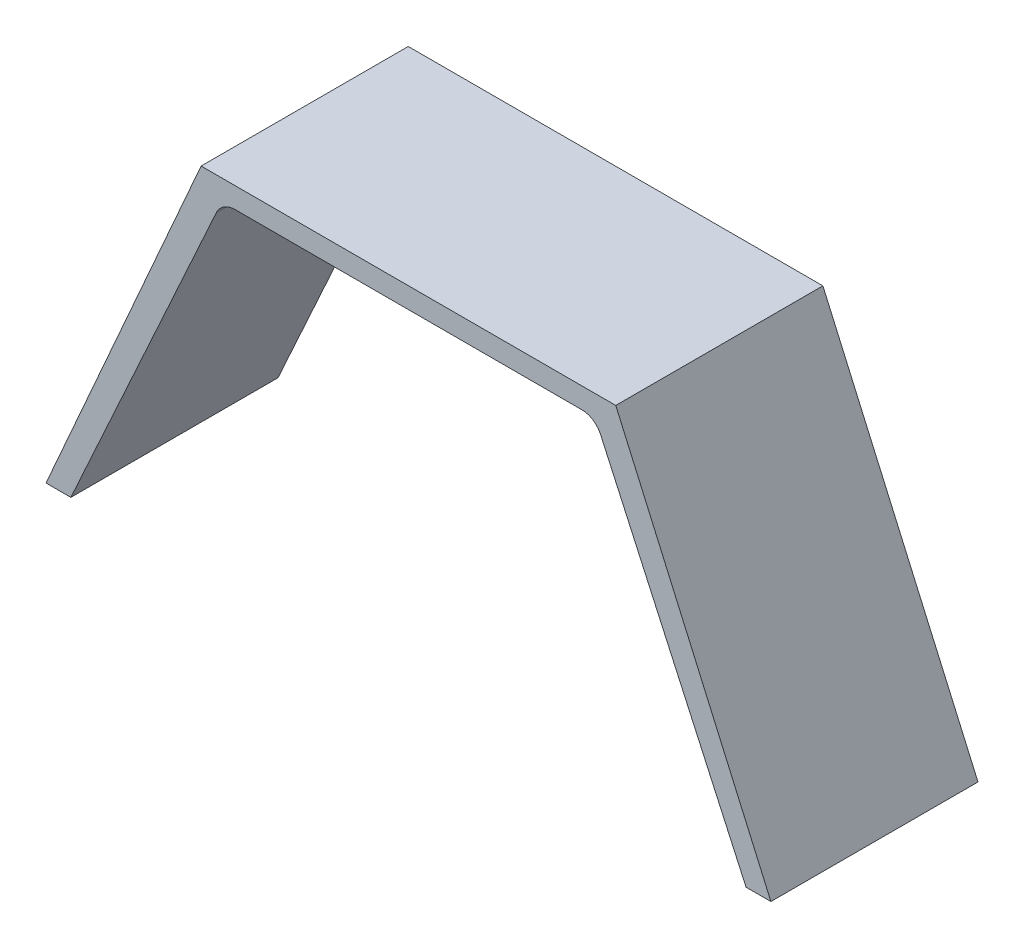
SolidWorks part; units mm, degrees
ref_plane "Front Plane" through (0, 0, 0) normal (0, 0, 1) x (1, 0, 0)
ref_plane "Top Plane" through (0, 0, 0) normal (0, 1, 0) x (1, 0, 0)
ref_plane "Right Plane" through (0, 0, 0) normal (1, 0, 0) x (0, 0, -1)
sketch "Sketch1" plane through (0, 0, 0) normal (0, 0, 1) x (1, 0, 0)
  line L0 (-87.5, 0) -> (87.5, 0)
  line L1 (-87.5, 0) -> (-50.05, 85)
  line L2 (-50.05, 85) -> (50.05, 85)
  line L3 (50.05, 85) -> (87.5, 0)
  point P4 (0, 0)
  dimension "D1" = 175
  dimension "D2" = 100.1
  dimension "D3" = 50.05
  dimension "D4" = 85
extrude "Boss-Extrude2" add sketch "Sketch1" along normal blind 50 contours L1 L2 L3 L0
sketch "Sketch3" plane through (0, 0, 50) normal (0, 0, 1) x (1, 0, 0)
  line L0 (-81.5, 0) -> (81.5, 0)
  line L1 (-87.5, 0) -> (87.5, 0) construction
  line L2 (81.5, 0) -> (45.05, 80)
  line L3 (45.05, 80) -> (-45.05, 80)
  line L4 (-45.05, 80) -> (-81.5, 0)
  line L5 (-50.05, 85) -> (50.05, 85) construction
  point P10 (0, 0)
  dimension "D1" = 163
  dimension "D2" = 6
  dimension "D3" = 90.1
  dimension "D4" = 45.05
  dimension "D5" = 5
extrude "Cut-Extrude1" cut sketch "Sketch3" against normal blind 50
fillet "Fillet1" radius 5 2 edges at (45.05, 80, 25) (-45.05, 80, 25)
sketch "Sketch5" plane through (73.2758, 32.2845, 0) normal (0.9151, 0.4032, 0) x (0, 0, -1)
  line L0 (0, 57.6053) -> (0, -35.2791) construction
  line L1 (-50, -35.2791) -> (0, -35.2791)
  line L2 (-50, -35.2791) -> (-50, -30.2791)
  line L3 (-50, -30.2791) -> (0, -30.2791)
  line L4 (0, -35.2791) -> (0, -30.2791)
  dimension "D1" = 5
